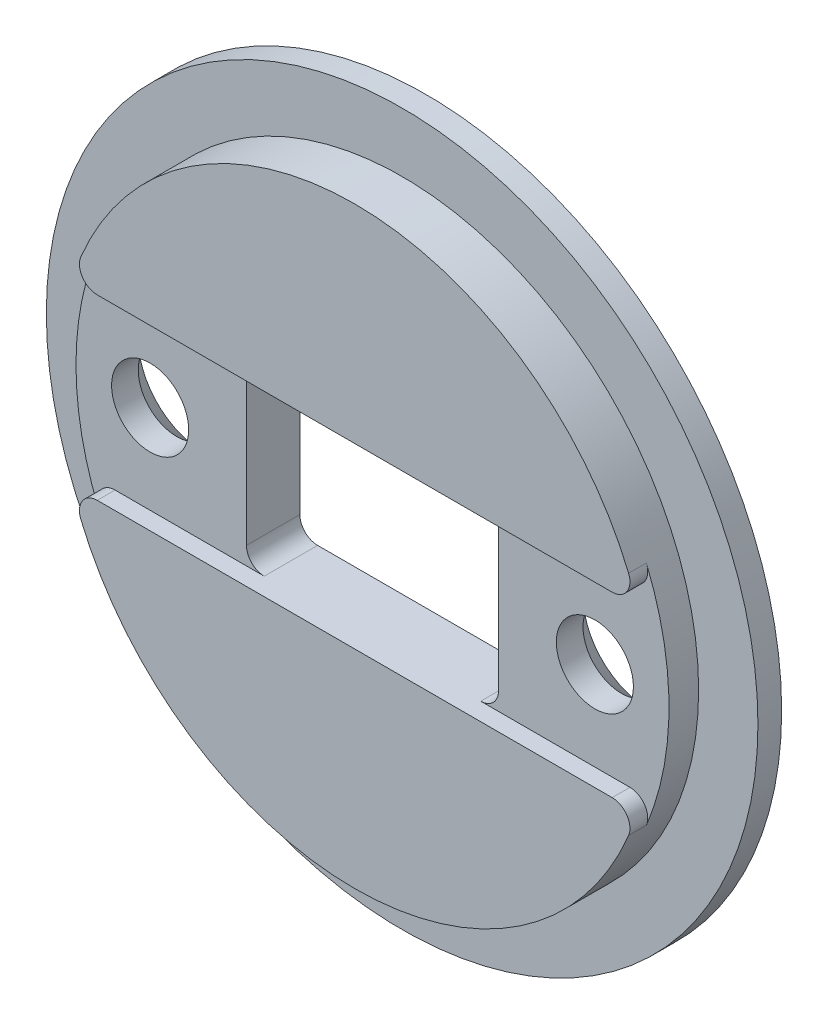
SolidWorks part; units mm, degrees
material "ABS"
ref_plane "Ebene vorne" through (0, 0, 0) normal (0, 0, 1) x (1, 0, 0)
ref_plane "Ebene oben" through (0, 0, 0) normal (0, 1, 0) x (1, 0, 0)
ref_plane "Ebene rechts" through (0, 0, 0) normal (1, 0, 0) x (0, 0, -1)
sketch "Skizze2" plane through (0, 0, 0) normal (0, 1, 0) x (1, 0, 0)
  line L0 (0, 0) -> (10, 0)
  line L2 (10, 0) -> (10, 1.6)
  line L3 (10, 1.6) -> (12, 1.6)
  line L4 (12, 1.6) -> (12, 2.4)
  line L5 (12, 2.4) -> (0, 2.4)
  line L6 (0, 2.4) -> (0, 0)
  dimension "D1" = 1.6
  dimension "D2" = 2
  dimension "D3" = 0.8
  dimension "D4" = 10
revolve "Rotation1" add sketch "Skizze2" angle 360 about L6
sketch "Skizze14" plane through (0, 0, 0) normal (0, 0, 1) x (1, 0, 0)
  line L1 (-4.25, -3) -> (4.25, -3)
  line L2 (-4.25, -3) -> (-4.25, 3)
  line L3 (-4.25, 3) -> (4.25, 3)
  line L4 (4.25, -3) -> (4.25, 3)
  line L5 (-4.25, -3) -> (4.25, 3) construction
  line L6 (-4.25, 3) -> (4.25, -3) construction
  point P0 (0, 0)
  dimension "D1" = 6
  dimension "D2" = 8.5
extrude "Schnitt-Linear austragen4" cut sketch "Skizze14" against normal through all
sketch "Skizze15" plane through (0, 0, 0) normal (0, 0, 1) x (1, 0, 0)
  line L0 (4.25, 3) -> (-4.25, 3) construction
  line L1 (12, -3) -> (-12, -3)
  line L2 (12, -3) -> (12, 3)
  line L3 (12, 3) -> (-12, 3)
  line L4 (-12, -3) -> (-12, 3)
  line L5 (12, -3) -> (-12, 3) construction
  line L6 (12, 3) -> (-12, -3) construction
  circle A0 centre (0, 0) radius 12 construction
  point P0 (0, 0)
extrude "Schnitt-Linear austragen5" cut sketch "Skizze15" against normal blind 0.6
fillet "Verrundung1" radius 0.6 4 edges at (-4.25, -3, -1.5) (4.25, 3, -1.5) (4.25, -3, -1.5) (-4.25, 3, -1.5)
fillet "Verrundung2" radius 0.6 4 edges at (-9.5394, 3, -0.3) (9.5394, -3, -0.3) (9.5394, 3, -0.3) (-9.5394, -3, -0.3)
hole_wizard "Formsenkung für M2 Linsensenkschraube mit Schlitz1" positions "Skizze16" profile "Skizze18" countersink size "M2" standard "DIN" end condition through all
sketch "Skizze16" plane through (0, 0, -2.4) normal (0, 0, 1) x (1, 0, 0)
  point P0 (-7.5, 0)
  point P2 (7.5, 0)
  dimension "D1" = 7.5
  dimension "D2" = 7.5
sketch "Skizze18" plane through (-7.5, 0, -2.4) normal (1, 0, 0) x (0, 1, 0)
  line L0 (0, 0) -> (0, 2.4)
  line L1 (0, 2.4) -> (1.3, 2.4)
  line L2 (1.3, 2.4) -> (1.3, 0.9)
  line L3 (1.3, 0.9) -> (2.2, 0)
  line L5 (2.2, 0) -> (0, 0)
  line L6 (-1.3, 0.9) -> (-2.2, 0) construction
  line L11 (0, -6.35) -> (0, 107.95) construction
  dimension "Bohrerdurchmesser" = 2.6
  dimension "Bohrungstiefe" = 2.4
  dimension "Senkdurchmesser (Oben)" = 4.4
  dimension "Senkwinkel (Oben)" = 90
